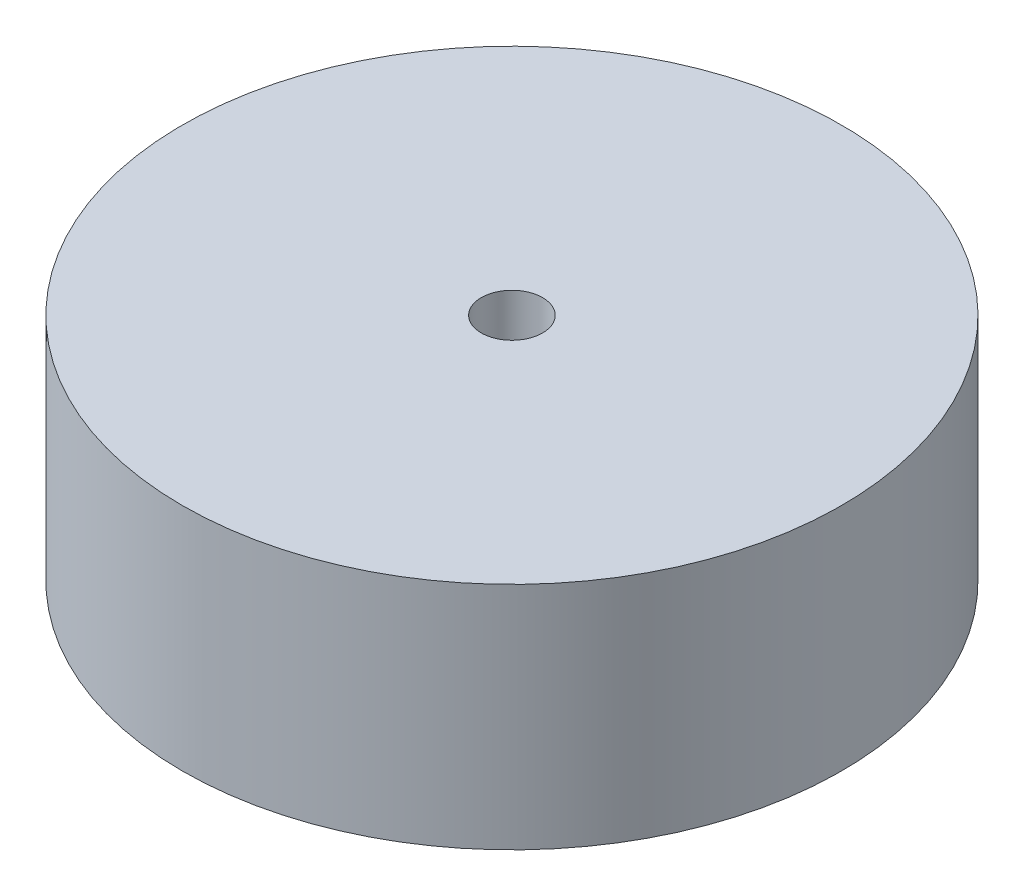
SolidWorks part; units mm, degrees
ref_plane "Front Plane" through (0, 0, 0) normal (0, 0, 1) x (1, 0, 0)
ref_plane "Top Plane" through (0, 0, 0) normal (0, 1, 0) x (1, 0, 0)
ref_plane "Right Plane" through (0, 0, 0) normal (1, 0, 0) x (0, 0, -1)
sketch "Sketch1" plane through (0, 0, 0) normal (0, 1, 0) x (1, 0, 0)
  circle A0 centre (0, 0) radius 21.5
extrude "Boss-Extrude1" add sketch "Sketch1" along normal blind 15
sketch "Sketch2" plane through (0, 0, 0) normal (0, 1, 0) x (1, 0, 0)
  circle A0 centre (0, 0) radius 2
extrude "Cut-Extrude1" cut sketch "Sketch2" against normal blind 9 and the other way blind 26
